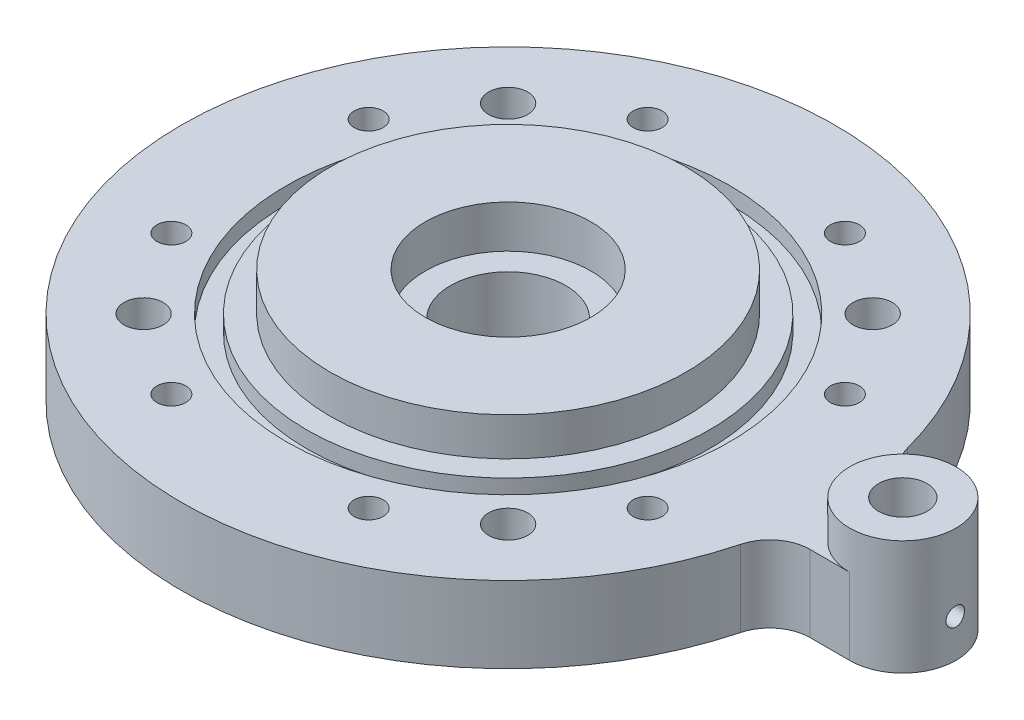
SolidWorks part; units mm, degrees
material "1060 Alloy"
ref_plane "Front" through (0, 0, 0) normal (0, 0, 1) x (1, 0, 0)
ref_plane "Top" through (0, 0, 0) normal (0, 1, 0) x (1, 0, 0)
ref_plane "Right" through (0, 0, 0) normal (1, 0, 0) x (0, 0, -1)
sketch "Sketch1" plane through (0, 0, 0) normal (0, 1, 0) x (1, 0, 0)
  line L0 (58.8962, 0) -> (68.0634, 0) construction
  line L1 (61.2588, 9.1672) -> (68.0634, 9.1672)
  line L2 (61.2588, -9.1672) -> (68.0634, -9.1672)
  line L3 (58.8962, 0) -> (77.2306, 0) construction
  line L4 (58.8962, 0) -> (56.3562, 0) construction
  arc A0 (54.4905, 14.3809) -> (54.4905, -14.3809) centre (0, 0) ccw
  circle A1 centre (0, 0) radius 56.3562 construction
  arc A2 (68.0634, -9.1672) -> (68.0634, 9.1672) centre (68.0634, 0) ccw
  arc A3 (54.4905, 14.3809) -> (61.2588, 9.1672) centre (61.2588, 16.1672) ccw
  arc A4 (61.2588, -9.1672) -> (54.4905, -14.3809) centre (61.2588, -16.1672) ccw
  point P5 (34.5422, 0)
  point P10 (55.6057, 9.1672)
  dimension "D1" = 112.7125
  dimension "D4" = 7
  dimension "D2" = 18.3344
  dimension "D3" = 18.3344
  dimension "D5" = 2.54
extrude "base" add sketch "Sketch1" along normal blind 13.175
sketch "Sketch2" plane through (0, 13.175, 0) normal (0, 1, 0) x (1, 0, 0)
  line L0 (68.0634, 9.1672) -> (68.0634, -9.1672) construction
  circle A0 centre (0, 0) radius 30.6705
  arc A1 (68.0634, -9.1672) -> (68.0634, 9.1672) centre (68.0634, 0) ccw construction
  circle A2 centre (68.0634, 0) radius 9.1672
  circle A3 centre (68.0634, 0) radius 4.1672
  dimension "D1" = 61.341
  dimension "D2" = 8.3344
sketch "Sketch3" plane through (0, 0, 0) normal (0, -1, 0) x (1, 0, 0)
  line L0 (0, 0) -> (77.2306, 0) construction
  line L1 (0, 0) -> (39.8499, -39.8499) construction
  circle A0 centre (0, 0) radius 44.45 construction
  circle A1 centre (-31.4309, -31.4309) radius 3.3734
  circle A2 centre (-31.4309, 31.4309) radius 3.3734
  circle A3 centre (31.4309, 31.4309) radius 3.3734
  circle A4 centre (31.4309, -31.4309) radius 3.3734
  arc A5 (68.0634, -9.1672) -> (68.0634, 9.1672) centre (68.0634, 0) ccw construction
  arc A6 (54.4905, 14.3809) -> (54.4905, -14.3809) centre (0, 0) ccw construction
  point P14 (0, 0)
  dimension "D1" = 88.9
  dimension "D2" = 6.7469
  dimension "D4" = 45
  dimension "D3" = 4
extrude "square bolt holes" cut sketch "Sketch3" against normal through all
sketch "Sketch4" plane through (0, 13.175, 0) normal (0, 1, 0) x (1, 0, 0)
  line L0 (0, 0) -> (0, 44.45) construction
  line L1 (0, 44.45) -> (0, 0) construction
  line L2 (0, 0) -> (17.0103, 41.0664) construction
  circle A0 centre (0, 0) radius 44.45 construction
  circle A1 centre (17.0103, 41.0664) radius 2.5
  dimension "D1" = 88.9
  dimension "D3" = 5
  dimension "D2" = 22.5
extrude "housing bolts" cut sketch "Sketch4" against normal blind 44.33
pattern_circular "CirPattern1" count 8 over 360 about axis through (0, 13.175, 0) along (0, 1, 0) of "housing bolts"
extrude "impeller cavity riser" add sketch "Sketch2" along normal blind 6.59
sketch "Sketch5" plane through (0, 19.765, 0) normal (0, 1, 0) x (1, 0, 0)
  circle A0 centre (0, 0) radius 14.2875
  dimension "D1" = 28.575
extrude "seal bore" cut sketch "Sketch5" against normal blind 7.35
sketch "Sketch6" plane through (0, 12.415, 0) normal (0, 1, 0) x (1, 0, 0)
  circle A0 centre (0, 0) radius 9.9375
  dimension "D1" = 19.875
extrude "bore" cut sketch "Sketch6" against normal blind 39.3
sketch "pressure tap plane alignment" plane through (0, 0, 0) normal (0, -1, 0) x (1, 0, 0)
  line L1 (0, 0) -> (56.3562, 0) construction
  line L2 (56.3562, 0) -> (56.3562, 56.3563) construction
  line L3 (56.3562, 56.3563) -> (0, 56.3562) construction
  circle A0 centre (0, 0) radius 56.3562 construction
  circle A1 centre (0, 0) radius 56.3562 construction
ref_plane "pressure tap plane" through (56.3562, 0, 0) normal (1, 0, 0) x (0, 0, -1)
sketch "Sketch9" plane through (56.3562, 0, 0) normal (1, 0, 0) x (0, 0, -1)
  line L0 (0, 0) -> (0, 13.175) construction
  line L1 (56.3562, 13.175) -> (-56.3563, 13.175) construction
  circle A0 centre (0, 6.5875) radius 1.5875
  dimension "D1" = 3.175
extrude "pressure tap" cut sketch "Sketch9" against normal blind 56.3562 and the other way through all
sketch "Sketch10" plane through (0, 13.175, 0) normal (0, 1, 0) x (1, 0, 0)
  circle A0 centre (68.0634, 0) radius 1.5875
  dimension "D1" = 3.175
extrude "pressure tap vertical hole" cut sketch "Sketch10" against normal blind 8.175
sketch "Sketch12" plane through (0, 13.175, 0) normal (0, 1, 0) x (1, 0, 0)
  circle A0 centre (0, 0) radius 34.7218
  circle A1 centre (0, 0) radius 38.2524
  dimension "D1" = 76.5048
  dimension "D2" = 69.4436
extrude "Cut-Extrude1" cut sketch "Sketch12" against normal blind 2.8245
equation "\"de\"= 0.43in\t\t\t'entrance eye diameter"
equation "\"d2\"= 2.1in \t\t\t'outer diameter of the impeller"
equation "\"d_exit\"= 0.18in \t\t'throat aka d1"
equation "\"theta\"= 12\t\t\t'angle of blades from inner to outer "
equation "\"impeller upper clearance\"= .5mm"
equation "\"impeller horizontal clearance\"= (\"d2\"*1.15 - \"d2\")/2 \t\t'clearance based on D2-D3 ratio for circular volute, ranges 1.15 to 1.2"
equation "\"impeller bottom clearance\"= .5mm"
equation "\"impeller base thickness\"= 2mm"
equation "\"impeller dowel diameter\"= 2mm"
equation "\"impeller bolt head diameter\"= \"m4 head bore diameter\""
equation "\"impeller bolt head depth\"= 4mm"
equation "\"impeller bolt stop depth\"= 3mm"
equation "\"impeller bolt bore\"= \"m4 clearance\""
equation "\"impeller shaft bore depth\"= 12mm"
equation "\"impeller shaft bore\"= 8mm"
equation "\"impeller boss depth\"= \"impeller shaft bore depth\"+\"impeller bolt stop depth\"+\"impeller bolt head depth\"-\"impeller base thickness\""
equation "\"impeller boss diameter\"= \"upper seal ID\""
equation "\"impeller dowel length\"= 2mm*2 + \"impeller shaft bore\""
equation "\"coupler motor shaft hole ID\"= 8mm"
equation "\"coupler OD\"= 17mm"
equation "\"coupler length\"= 25mm"
equation "\"motor OD\"= 64mm"
equation "\"motor shaft diameter\"= 8mm"
equation "\"motor shaft pride\"= 32mm"
equation "\"motor to bearing plate distance\"= \"motor shaft pride\" + 2mm +\"coupler length\"/2"
equation "\"square plate bolt bore\"= \"m8 clearance\""
equation "\"square plate bolt head diameter\"= 13.5mm"
equation "\"square plate bolt pattern diameter\"= 3.5in"
equation "\"motor mount center bore\"= \"coupler OD\"+ 4mm"
equation "\"motor mount post radius\"= ( 3 * \"square plate bolt bore\" ) / 2"
equation "\"motor mount m4 screw hole diameter\"= 4mm"
equation "\"motor mount m4 head diameter\"= 7.25mm"
equation "\"motor mount m4 head depth\"= 4mm"
equation "\"motor mount m4 pattern diamater\"= 30mm"
equation "\"motor mount plate thickness\"= 8mm + \"motor mount m4 head depth\""
equation "\"shaft coupler section diameter\"= 8mm"
equation "\"shaft coupler section length\"= \"motor to bearing plate distance\" - \"motor shaft pride\" - 2mm"
equation "\"shaft bearing section diameter\"= \"bearing ID\""
equation "\"shaft bearing section length\"= \"bearing plate stop depth\" + \"bearing depth\""
equation "\"shaft bearing stop diameter\"= \"bearing ID\" + 4mm"
equation "\"shaft bearing stop length\"= 3mm"
equation "\"impeller cavity center height\"= \"impeller bottom clearance\" + \"impeller upper clearance\" + \"impeller center height\""
equation "\"impeller cavity diameter\"= 2 * \"impeller horizontal clearance\" + \"d2\" \t\t\t\t\t\t\t\t\t'called D3 analytically"
equation "\"impeller cavity outer height\"= \"impeller bottom clearance\" + \"impeller upper clearance\" + \"impeller base thickness\" + \"b2\" \t\t'this is height at impeller diameter d2, not at d3"
equation "\"impeller housing thickness\"= \"impeller housing exit threaded diameter\" + 2*\"impeller housing outlet grip\""
equation "\"impeller housing diameter\"= \"square plate bolt pattern diameter\" + 2*\"motor mount post radius\""
equation "\"impeller housing bolt count\"= 8"
equation "\"impeller housing bolt diameter\"= \"m6 clearance\""
equation "\"impeller housing bolt pattern diameter\"= 3.5in"
equation "\"impeller housing threaded inlet diameter\"= 0.515625in \t'this is the 33/64 drill size for 9/16-18 fitting, expecting swagelok SS-8FK0-1-6STH fitting"
equation "\"impeller housing threaded inlet depth\"= 10mm"
equation "\"impeller housing exit threaded diameter\"= 0.515625in \t\t'this is the 33/64 drill size for 9/16-18 fitting, expecting swagelok SS-8FK0-1-6STH fitting"
equation "\"impeller housing exit threaded depth\"= 10mm"
equation "\"impeller housing diffuser conical angle\"=10"
equation "\"impeller housing diffuser tangent angle\"=5"
equation "\"impeller housing outlet grip\"= 5mm"
equation "\"D1@Sketch1\"=\"impeller housing diameter\""
equation "\"D1@base\" = \"upper seal plate thickness\""
equation "\"D1@Sketch2\"=\"impeller cavity diameter\""
equation "\"D1@Sketch3\"=\"square plate bolt pattern diameter\""
equation "\"D2@Sketch3\"=\"m8 tap\""
equation "\"D1\"= \"upper seal plate thickness\" - 2mm"
equation "\"D1@Sketch4\"=\"impeller housing bolt pattern diameter\""
equation "\"D2@Sketch4\"=360/\"impeller housing bolt count\"/2"
equation "\"D3@Sketch4\"=\"m6 tap\""
equation "\"D1@CirPattern1\"=\"impeller housing bolt count\""
equation "\"D1@impeller cavity riser\" = \"upper seal plate riser\""
equation "\"D1@Sketch5\" = \"upper seal OD\""
equation "\"D1@seal bore\" = \"upper seal bore\""
equation "\"D1@Sketch6\" = \"upper seal ID\" + 4mm"
equation "\"D1@Sketch9\" = \"upper seal plate pressure hole diameter\""
equation "\"D1@pressure tap\"=\"impeller housing diameter\"/2"
equation "\"de_length\"= 10mm\t\t'entrance eye consistent length"
equation "\"square plate bolt head depth\"= 8mm"
equation "\"shaft impeller section diameter\"= \"impeller shaft bore\""
equation "\"shaft impeller section length\"= \"upper seal plate thickness\" + \"upper seal plate riser\" + \"impeller bottom clearance\" + \"impeller base thickness\" - \"impeller bolt head depth\" - \"impeller bolt stop depth\""
equation "\"impeller housing diffuser final diameter\"= .38in\t\t'aka d2'"
equation "\"D2@Sketch1\" = \"upper seal plate pressure tap diameter\" + \"upper seal plate pressure tap grip\" * 2"
equation "\"D3@Sketch1\" = \"upper seal plate pressure tap diameter\" + \"upper seal plate pressure tap grip\" * 2"
equation "\"D2@pressure tap\"=\"big seal plate pressure tap diameter\"/2+\"big seal plate pressure tap grip\""
equation "\"D2@Sketch2\" = \"upper seal plate pressure tap diameter\""
equation "\"D1@Sketch10\" = \"upper seal plate pressure hole diameter\""
equation "\"D1@pressure tap vertical hole\"= \"upper seal plate thickness\" / 2 + \"upper seal plate pressure hole diameter\" / 2"
equation "\"end mill size\"= 0.375in\t'for 3/8 endmill"
equation "\"m6 clearance\"= 0.234375in\t'this is 15/64 bit = 5.95mm, could use 6mm bit, B bit for 6.04mm or 1/4 bit for 6.35mm"
equation "\"m6 tap\"= 5mm\t\t\t'5mm is appropriate, could use 13/64 or #5,6,7"
equation "\"m6 head bore diameter\"= 11mm\t\t"
equation "\"m6 head bore depth\"= 7mm\t'actual is 6mm"
equation "\"m8 clearance\"= 0.3125in\t'this is 5/16in for 7.93mm, could use 8mm, O,P, or 21/64"
equation "\"m8 tap\"= 0.265625in\t\t'this is 17/64 for 6.746875mm"
equation "\"m8 head bore diameter\"= 14mm"
equation "\"m8 head bore depth\"= 9mm\t'actual is 8mm"
equation "\"ce\"= 3.14*\"de\"\t\t'entrance eye circumference"
equation "\"s_open\"= \"av\"/\"b1\"\t\t'width of open area"
equation "\"impeller center height\"= \"impeller base thickness\" + \"b1\"\t'impeller height at de"
equation "\"impeller outer height\"= \"impeller base thickness\" + \"b2\"\t'impeller height at de"
equation "\"lower seal OD\"= .917in\t\t'this is https://www.mcmaster.com/#9281k121/=174001b"
equation "\"lower seal ID\"= .375in"
equation "\"lower seal depth\"= .625in + .218in"
equation "\"lower seal bore\"= \"lower seal depth\" + 1mm"
equation "\"upper seal OD\"= 1.125in\t'this is https://www.mcmaster.com/#5154t33/=173zuau, needs to be visually inspected before machining!"
equation "\"upper seal ID\"= 0.625in"
equation "\"upper seal depth\"= .25in\t'aka height; these values need to be confirmed by inspection!! We may want to compress the height."
equation "\"upper seal bore\"= \"upper seal depth\" + 1mm"
equation "\"lower seal plate lip depth\"= 2mm"
equation "\"lower seal plate lip ID\"= \"lower seal OD\" - 3mm"
equation "\"lower seal plate thickness\"= \"lower seal plate lip depth\" + \"lower seal bore\""
equation "\"shaft lower seal section diameter\"= \"lower seal ID\""
equation "\"shaft lower seal section length\"= \"lower seal plate thickness\" + 1mm"
equation "\"upper seal plate thickness\"= \"upper seal plate pressure hole diameter\"+10mm"
equation "\"upper seal plate lip ID\"= \"upper seal OD\" - 3mm"
equation "\"upper seal plate riser\"= 6.59mm \t\t'this number needs to be read from the housing file"
equation "\"upper seal plate pressure hole diameter\"= .125in\t'this is 1/8 drill "
equation "\"upper seal plate pressure tap diameter\"= .328125in \t'this is 21/64 drill for a 1/8 ANPT tap"
equation "\"upper seal plate pressure tap grip\"= 5mm\t\t'this is the area around the tap so it doesn't crack"
equation "\"upper seal plate pressure tap depth\"= 12"
equation "\"bearing OD\"= 30mm"
equation "\"bearing ID\"= 10mm"
equation "\"bearing depth\"= 9mm"
equation "\"bearing outer race thickness\"= 1mm"
equation "\"bearing inner race thickness\"= 1mm"
equation "\"bearing bore\"= \"bearing depth\" + 1mm"
equation "\"z\"= 8\t\t\t\t'number of blades"
equation "\"b2\"= .2in\t\t\t'tip height from disc surface at d2; slightly higher than d_exit"
equation "\"b1\"= \"b2\" + (\"d2\"/2 - \"de\"/2)*tan(\"theta\") \t\t\t'tip height from disc surface at inlet eye"
equation "\"ae\"= 3.14*(\"de\"^2)/4\t\t'entrance eye area'"
equation "\"av_ratio\"= .325\t\t'ratio of av/ae at N_s of 470, range is .275 to .375, .325 ideal. High ratio means bigger area means smaller blades"
equation "\"av\"= \"ae\"*\"av_ratio\"\t\t'area between just two blades"
equation "\"s\"=\"ce\" - \"z\"*\"s_open\""
equation "\"bearing plate stop ID\"= \"bearing OD\" - 4mm"
equation "\"bearing plate stop depth\"= 3mm"
equation "\"bearing plate thickness\"= \"bearing bore\" + \"bearing plate stop depth\" + \"shaft bearing stop length\""
equation "\"m4 clearance\"= 0.171875in \t'this is 11/64 bit for 4.36mm"
equation "\"m4 tap\"= 0.125in\t\t'this is 1/8 bit for 3.17mm"
equation "\"m4 head bore diameter\"= 7.5mm"
equation "\"m4 head bore depth\"= 5mm\t'actual is ~4mm"
equation "\"big o-ring thickness\"= .139in"
equation "\"big o-ring OD\"= 2.734in"
equation "\"big o-ring ID\"= 3.012in"
equation "\"big o-ring groove depth\"= \"big o-ring thickness\"*4/5"
equation "\"D1@Sketch12\"=\"big o-ring ID\""
equation "\"D2@Sketch12\"=\"big o-ring OD\""
equation "\"D1@Cut-Extrude1\"=\"big o-ring groove depth\""
equation "\"min blade thickness\"= .15in"
